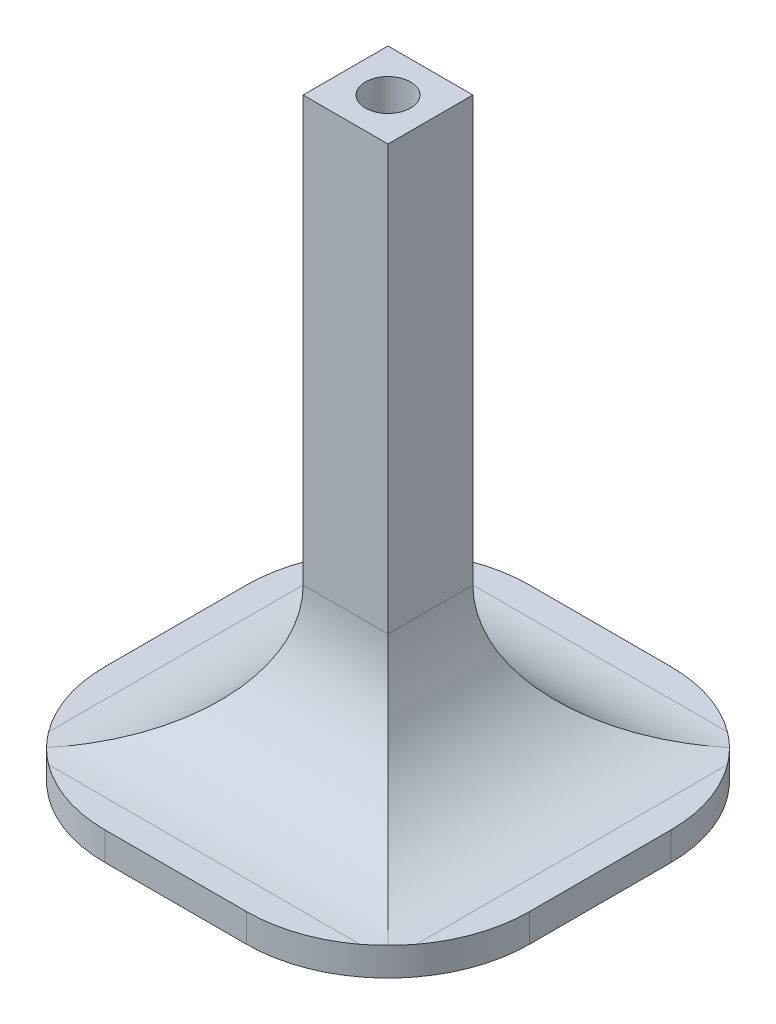
SolidWorks part; units mm, degrees
ref_plane "Front Plane" through (0, 0, 0) normal (0, 0, 1) x (1, 0, 0)
ref_plane "Top Plane" through (0, 0, 0) normal (0, 1, 0) x (1, 0, 0)
ref_plane "Right Plane" through (0, 0, 0) normal (1, 0, 0) x (0, 0, -1)
sketch "Sketch2" plane through (0, 0, 0) normal (0, 1, 0) x (1, 0, 0)
  line L1 (0, 0) -> (30, 0)
  line L2 (0, 0) -> (0, 30)
  line L3 (0, 30) -> (30, 30)
  line L4 (30, 0) -> (30, 30)
  dimension "D1" = 30
  dimension "D2" = 30
extrude "Boss-Extrude1" add sketch "Sketch2" along normal blind 2
sketch "Sketch3" plane through (0, 2, 0) normal (0, 1, 0) x (1, 0, 0)
  line L0 (15, 30) -> (15, 0) construction
  line L1 (30, 30) -> (0, 30) construction
  line L2 (0, 0) -> (30, 0) construction
  line L3 (0, 15) -> (30, 15) construction
  line L4 (0, 30) -> (0, 0) construction
  line L5 (30, 0) -> (30, 30) construction
  line L7 (12, 12) -> (18, 12)
  line L8 (12, 12) -> (12, 18)
  line L9 (12, 18) -> (18, 18)
  line L10 (18, 12) -> (18, 18)
  line L11 (12, 12) -> (18, 18) construction
  line L12 (12, 18) -> (18, 12) construction
  point P12 (15, 15)
  dimension "D1" = 6
  dimension "D2" = 6
extrude "Boss-Extrude2" add sketch "Sketch3" along normal blind 40
fillet "Fillet1" radius 10 1 edges at (0, 1, 0)
fillet "Fillet2" radius 10 1 edges at (0, 1, -30)
fillet "Fillet3" radius 10 1 edges at (30, 1, 0)
fillet "Fillet4" radius 10 1 edges at (30, 1, -30)
fillet "Fillet5" radius 10 1 edges at (18, 2, -15)
fillet "Fillet6" radius 10 1 edges at (12, 2, -15)
fillet "Fillet7" radius 10 1 edges at (15, 2, -18)
fillet "Fillet8" radius 10 1 edges at (15, 2, -12)
sketch "Sketch4" plane through (0, 42, 0) normal (0, 1, 0) x (1, 0, 0)
  line L0 (15, 18) -> (15, 12) construction
  line L1 (18, 18) -> (12, 18) construction
  line L2 (12, 12) -> (18, 12) construction
  line L3 (12, 15) -> (18, 15) construction
  line L4 (12, 18) -> (12, 12) construction
  line L5 (18, 12) -> (18, 18) construction
  circle A0 centre (15, 15) radius 1.6
  dimension "D1" = 3.2
extrude "Cut-Extrude1" cut sketch "Sketch4" against normal blind 8
